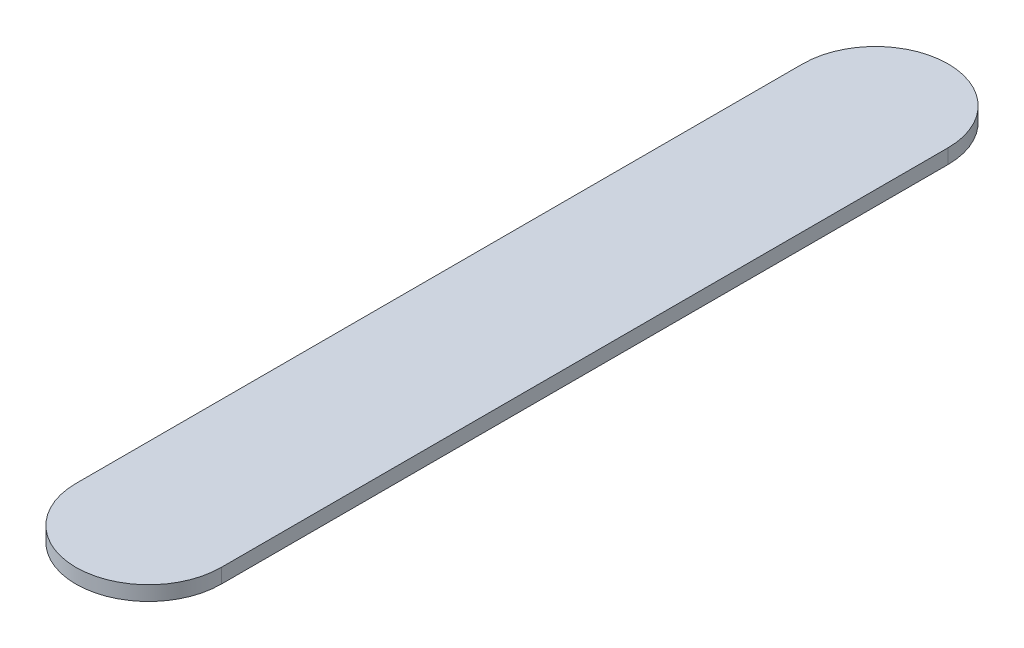
SolidWorks part; units mm, degrees
ref_plane "Front Plane" through (0, 0, 0) normal (0, 0, 1) x (1, 0, 0)
ref_plane "Top Plane" through (0, 0, 0) normal (0, 1, 0) x (1, 0, 0)
ref_plane "Right Plane" through (0, 0, 0) normal (1, 0, 0) x (0, 0, -1)
sketch "Sketch1" plane through (0, 0, 0) normal (0, 1, 0) x (1, 0, 0)
  line L2 (0, 0) -> (0, 50)
  line L4 (10, 0) -> (10, 50)
  arc A0 (10, 50) -> (0, 50) centre (5, 50) ccw
  arc A1 (0, 0) -> (10, 0) centre (5, 0) ccw
  dimension "D3" = 5
  dimension "D4" = 5
  dimension "D1" = 10
  dimension "D2" = 50
extrude "Boss-Extrude1" add sketch "Sketch1" along normal blind 1
